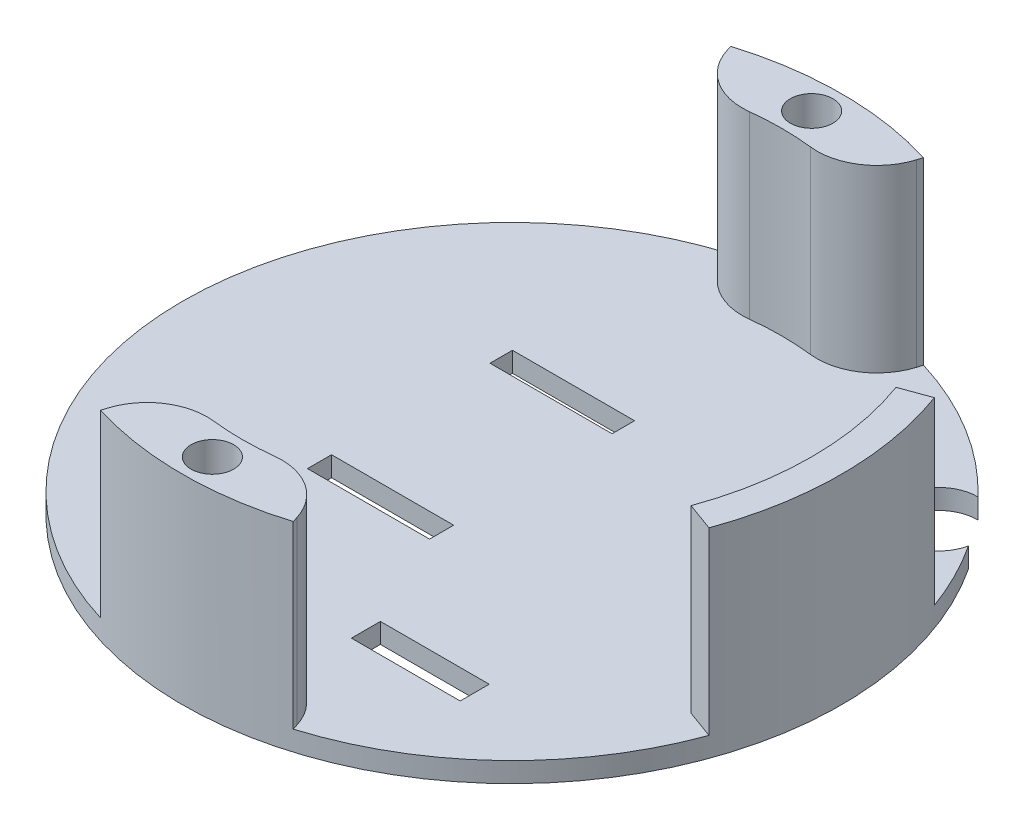
SolidWorks part; units mm, degrees
ref_plane "Front Plane" through (0, 0, 0) normal (0, 0, 1) x (1, 0, 0)
ref_plane "Top Plane" through (0, 0, 0) normal (0, 1, 0) x (1, 0, 0)
ref_plane "Right Plane" through (0, 0, 0) normal (1, 0, 0) x (0, 0, -1)
sketch "Sketch2" plane through (0, 0, 0) normal (0, 1, 0) x (1, 0, 0)
  circle A0 centre (0, 0) radius 69.85
  dimension "D1" = 139.7
extrude "Boss-Extrude1" add sketch "Sketch2" along normal blind 4.2333
sketch "Sketch3" plane through (0, 4.2333, 0) normal (0, 1, 0) x (1, 0, 0)
  line L0 (-20.4222, 66.7979) -> (-16.709, 54.6528)
  line L5 (20.4222, 66.7979) -> (16.709, 54.6528)
  line L6 (16.709, -54.6528) -> (20.4222, -66.7979)
  line L7 (-16.709, -54.6528) -> (-20.4222, -66.7979)
  arc A6 (20.4222, 66.7979) -> (-20.4222, 66.7979) centre (0, 0) ccw
  arc A7 (-16.709, -54.6528) -> (16.709, -54.6528) centre (0, 0) ccw
  arc A8 (-20.4222, -66.7979) -> (20.4222, -66.7979) centre (0, 0) ccw
  arc A9 (16.709, 54.6528) -> (-16.709, 54.6528) centre (0, 0) ccw
  circle M3 centre (0, 0) radius 69.85
  dimension "D1" = 114.3
extrude "Boss-Extrude2" add sketch "Sketch3" along normal blind 38.1 contours A7 L7 L6 M3 | A9 L5 L0 M3
fillet "Fillet3" radius 12.7 1 edges at (-16.709, 23.2833, -54.6528) type face fillet first side face at (-18.5656, 23.2833, -60.7254) second side face at (0, 23.2833, -55.9014)
fillet "Fillet4" radius 12.7 1 edges at (16.709, 23.2833, 54.6528) type face fillet first side face at (0, 23.2833, 55.9014) second side face at (18.5656, 23.2833, 60.7254)
fillet "Fillet5" radius 12.7 1 edges at (-16.709, 23.2833, 54.6528) type face fillet first side face at (-5.1625, 23.2833, 56.3139) second side face at (-18.5656, 23.2833, 60.7254)
sketch "Sketch4" plane through (0, 4.2333, 0) normal (0, 1, 0) x (1, 0, 0)
  line L0 (59.6705, 21.7183) -> (65.6375, 23.8901)
  line L1 (59.6705, -21.7183) -> (65.6375, -23.8901)
  arc A0 (65.6375, -23.8901) -> (65.6375, 23.8901) centre (0, 0) ccw
  arc A1 (59.6705, -21.7183) -> (59.6705, 21.7183) centre (0, 0) ccw
  dimension "D1" = 127
extrude "Boss-Extrude3" add sketch "Sketch4" along normal blind 38.1
sketch "Sketch5" plane through (0, 42.3333, 0) normal (0, 1, 0) x (1, 0, 0)
  circle A0 centre (0, 63.5) radius 4.5085
  circle A1 centre (0, -63.5) radius 4.5085
  arc A3 (-20.4222, -66.7979) -> (20.4222, -66.7979) centre (0, 0) ccw construction
  point P7 (0, -69.85)
  dimension "D1" = 9.017
  dimension "D2" = 9.017
  dimension "D3" = 127
  dimension "D4" = 6.35
extrude "Cut-Extrude1" cut sketch "Sketch5" against normal through all both and the other way through all
fillet "Fillet6" radius 12.7 1 edges at (16.709, 23.2833, -54.6528) type face fillet first side face at (5.1625, 23.2833, -56.3139) second side face at (18.5656, 23.2833, -60.7254)
sketch "Sketch6" plane through (0, 4.2333, 0) normal (0, 1, 0) x (1, 0, 0)
  line L1 (-25.8818, 25.9764) -> (0, 25.9764)
  line L2 (-25.8818, 25.9764) -> (-25.8818, 21.2144)
  line L3 (-25.8818, 21.2144) -> (0, 21.2144)
  line L4 (0, 25.9764) -> (0, 21.2144)
  line L5 (-25.8818, -12.3677) -> (0, -12.3677)
  line L6 (-25.8818, -12.3677) -> (-25.8818, -17.4698)
  line L7 (-25.8818, -17.4698) -> (0, -17.4698)
  line L8 (0, -12.3677) -> (0, -17.4698)
  line L9 (9.8968, -37.7846) -> (32.9561, -37.7846)
  line L10 (9.8968, -37.7846) -> (9.8968, -43.9338)
  line L11 (9.8968, -43.9338) -> (32.9561, -43.9338)
  line L12 (32.9561, -37.7846) -> (32.9561, -43.9338)
  circle A0 centre (50.292, 40.132) radius 8.255
  dimension "D2" = 16.51
  dimension "D1" = 0
  dimension "D3" = 40.132
  dimension "D4" = 50.292
extrude "Cut-Extrude2" cut sketch "Sketch6" against normal through all both
